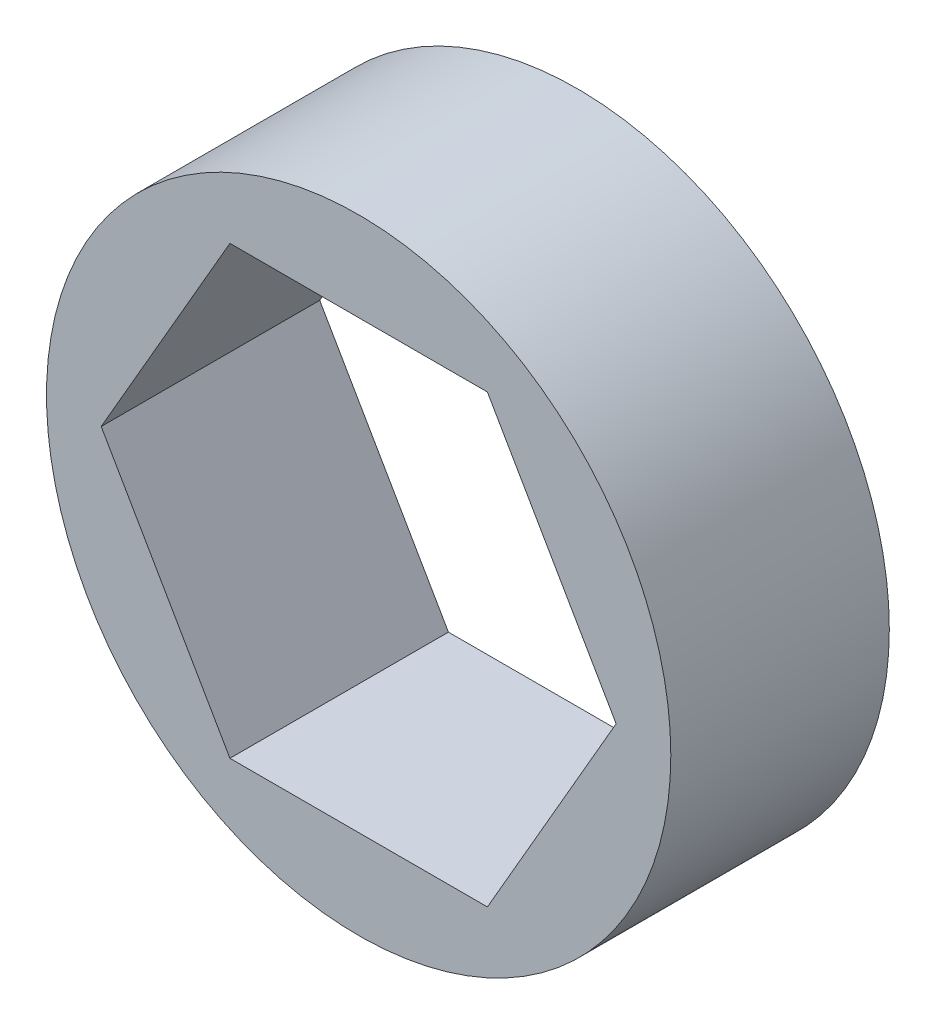
SolidWorks part; units mm, degrees
material "PET"
ref_plane "Front Plane" through (0, 0, 0) normal (0, 0, 1) x (1, 0, 0)
ref_plane "Top Plane" through (0, 0, 0) normal (0, 1, 0) x (1, 0, 0)
ref_plane "Right Plane" through (0, 0, 0) normal (1, 0, 0) x (0, 0, -1)
sketch "Sketch1" plane through (0, 0, 0) normal (0, 0, 1) x (1, 0, 0)
  line L1 (-7.3323, 0) -> (-3.6662, -6.35)
  line L2 (-3.6662, -6.35) -> (3.6662, -6.35)
  line L3 (3.6662, -6.35) -> (7.3323, 0)
  line L4 (7.3323, 0) -> (3.6662, 6.35)
  line L5 (3.6662, 6.35) -> (-3.6662, 6.35)
  line L6 (-3.6662, 6.35) -> (-7.3323, 0)
  circle A1 centre (0, 0) radius 8.89
  circle A2 centre (0, 0) radius 6.35 construction
  point P1 (0, 0)
  dimension "D1" = 17.78
  dimension "D2" = 12.7
extrude "Boss-Extrude1" add sketch "Sketch1" along normal mid plane 6.223
